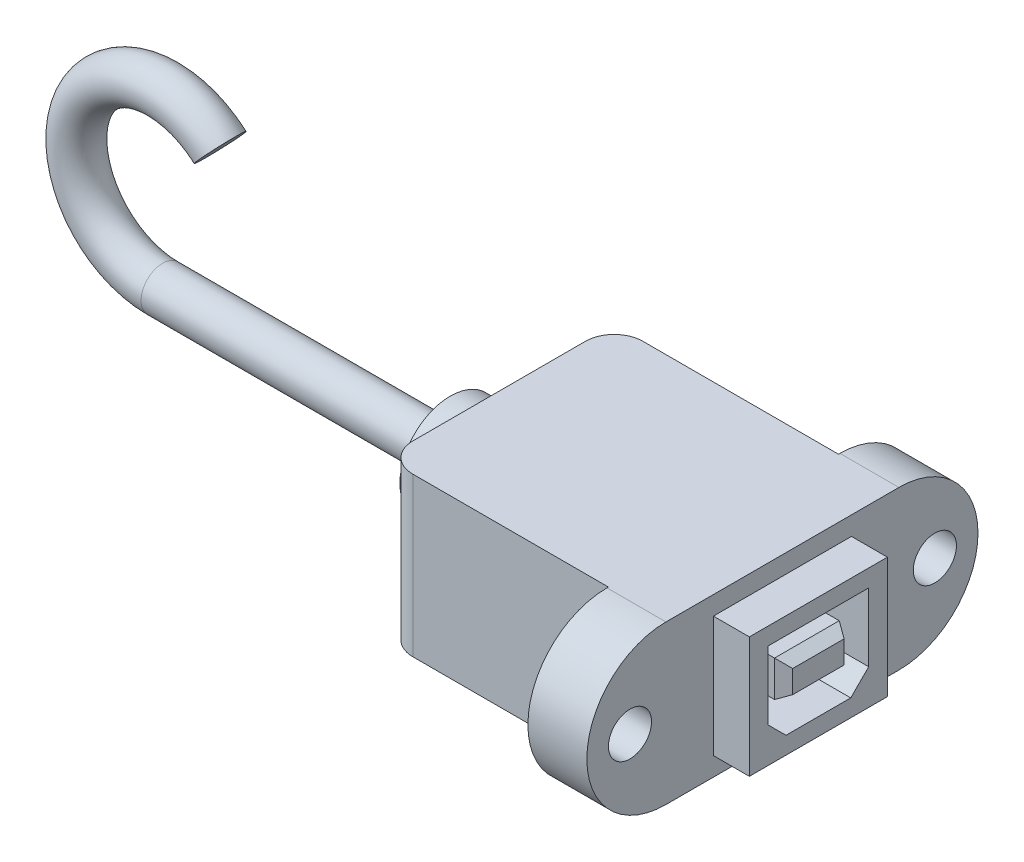
SolidWorks part; units mm, degrees
ref_plane "Front" through (0, 0, 0) normal (0, 0, 1) x (1, 0, 0)
ref_plane "Top" through (0, 0, 0) normal (0, 1, 0) x (1, 0, 0)
ref_plane "Right" through (0, 0, 0) normal (1, 0, 0) x (0, 0, -1)
sketch "Sketch1" plane through (0, 0, 0) normal (0, 1, 0) x (1, 0, 0)
  line L0 (0, 0) -> (0, 20.32)
  line L1 (0, 20.32) -> (19.812, 20.32)
  line L2 (19.812, 20.32) -> (19.812, 27.432)
  line L3 (19.812, 27.432) -> (25.019, 27.432)
  line L4 (25.019, 27.432) -> (25.019, -7.112)
  line L5 (25.019, -7.112) -> (19.812, -7.112)
  line L6 (19.812, -7.112) -> (19.812, 0)
  line L7 (19.812, 0) -> (0, 0)
  dimension "D1" = 34.544
  dimension "D2" = 5.207
  dimension "D3" = 20.32
  dimension "D4" = 19.812
extrude "Boss-Extrude1" add sketch "Sketch1" along normal blind 13.97
sketch "Sketch2" plane through (25.019, 0, 0) normal (1, 0, 0) x (0, 0, -1)
  line L0 (-7.112, 6.985) -> (4.064, 6.985) construction
  line L1 (4.064, 12.319) -> (16.256, 12.319)
  line L2 (4.064, 12.319) -> (4.064, 1.651)
  line L3 (4.064, 1.651) -> (16.256, 1.651)
  line L4 (16.256, 12.319) -> (16.256, 1.651)
  line L5 (-7.112, 13.97) -> (-7.112, 0) construction
  line L6 (4.064, 6.985) -> (10.16, 1.651) construction
  line L7 (10.16, 1.651) -> (10.16, 0) construction
  line L8 (-7.112, 0) -> (27.432, 0) construction
  dimension "D1" = 10.668
  dimension "D2" = 12.192
extrude "Boss-Extrude2" add sketch "Sketch2" along normal blind 3.175
sketch "Sketch3" plane through (28.194, 0, 0) normal (1, 0, 0) x (0, 0, -1)
  line L0 (5.715, 10.795) -> (14.605, 10.795)
  line L1 (14.605, 10.795) -> (14.605, 4.7625)
  line L2 (14.605, 4.7625) -> (13.0175, 3.175)
  line L3 (13.0175, 3.175) -> (7.3025, 3.175)
  line L4 (7.3025, 3.175) -> (5.715, 4.7625)
  line L5 (5.715, 4.7625) -> (5.715, 10.795)
  line L6 (10.16, 1.651) -> (10.16, 5.3975) construction
  line L7 (7.3025, 8.5725) -> (13.0175, 8.5725)
  line L8 (7.3025, 8.5725) -> (7.3025, 5.3975)
  line L9 (7.3025, 5.3975) -> (13.0175, 5.3975)
  line L10 (13.0175, 8.5725) -> (13.0175, 5.3975)
  line L11 (4.064, 1.651) -> (16.256, 1.651) construction
  line L12 (10.16, 5.3975) -> (7.3025, 6.985) construction
  line L13 (7.3025, 6.985) -> (4.064, 6.985) construction
  line L14 (4.064, 12.319) -> (4.064, 1.651) construction
  line L15 (13.0175, 3.175) -> (13.0175, 1.651) construction
  line L16 (4.064, 1.651) -> (16.256, 1.651) construction
  line L17 (10.16, 10.795) -> (10.16, 12.319) construction
  line L18 (16.256, 12.319) -> (4.064, 12.319) construction
  point P14 (10.16, 3.175)
  dimension "D1" = 5.715
  dimension "D2" = 3.175
  dimension "D3" = 7.62
  dimension "D4" = 8.89
  dimension "D5" = 135
  dimension "D6" = 1.5875
extrude "Cut-Extrude1" cut sketch "Sketch3" against normal blind 7.62
chamfer "Chamfer1" distance 1.016 angle 30 4 edges at (28.194, 6.985, -13.0175) (28.194, 5.3975, -10.16) (28.194, 6.985, -7.3025) (28.194, 8.5725, -10.16) first distance on face at (24.384, 6.985, -13.0175) first distance on face at (24.384, 5.3975, -10.16) first distance on face at (24.384, 6.985, -7.3025) first distance on face at (24.384, 8.5725, -10.16)
sketch "Sketch4" plane through (25.019, 0, 0) normal (1, 0, 0) x (0, 0, -1)
  line L0 (-7.112, 13.97) -> (27.432, 13.97) construction
  line L1 (-7.112, 0) -> (27.432, 0) construction
  line L2 (27.432, 13.97) -> (27.432, 0) construction
  line L3 (-7.112, 13.97) -> (-7.112, 0) construction
  line L4 (-0.127, 0) -> (-7.112, 0)
  line L5 (-7.112, 0) -> (-7.112, 13.97)
  line L6 (-7.112, 13.97) -> (-0.127, 13.97)
  line L7 (20.447, 13.97) -> (27.432, 13.97)
  line L8 (27.432, 13.97) -> (27.432, 0)
  line L9 (27.432, 0) -> (20.447, 0)
  line L10 (-3.302, 6.985) -> (10.16, 13.97) construction
  line L11 (10.16, 13.97) -> (23.622, 6.985) construction
  line L12 (25.527, 6.985) -> (27.432, 6.985) construction
  arc A0 (-0.127, 13.97) -> (-0.127, 0) centre (-0.127, 6.985) ccw
  arc A1 (20.447, 13.97) -> (20.447, 0) centre (20.447, 6.985) cw
  circle A4 centre (-3.302, 6.985) radius 1.905
  circle A5 centre (23.622, 6.985) radius 1.905
  line M3 (-7.112, 0) -> (27.432, 0)
  line M4 (27.432, 0) -> (27.432, 13.97)
  line M5 (27.432, 13.97) -> (-7.112, 13.97)
  line M6 (-7.112, 13.97) -> (-7.112, 0)
  dimension "D1" = 26.924
  dimension "D2" = 3.81
  dimension "D3" = 3.81
extrude "Cut-Extrude2" cut sketch "Sketch4" against normal through all contours A0 M5 M6 | A0 L5 M3 | A4 | A1 L8 M5 | A1 M4 M3 | A5 region at (25.019, 1.5602, 5.5518) region at (25.019, 12.4098, 5.5518) region at (25.019, 1.5602, -25.8718) region at (25.019, 12.4098, -25.8718) region at (25.019, 6.985, 3.302) region at (25.019, 6.985, -23.622)
fillet "Fillet1" radius 2.54 2 edges at (0, 6.985, 0) (0, 6.985, -20.32)
sketch "Sketch5" plane through (0, 0, 0) normal (-1, 0, 0) x (0, 0, 1)
  line L0 (-17.78, 6.985) -> (-10.16, 6.985) construction
  line L1 (-17.78, 13.97) -> (-17.78, 0) construction
  line L2 (-10.16, 6.985) -> (-10.16, 13.97) construction
  line L3 (-17.78, 13.97) -> (-2.54, 13.97) construction
  circle A0 centre (-10.16, 6.985) radius 4.445
  dimension "D1" = 8.89
extrude "Boss-Extrude3" add sketch "Sketch5" along normal blind 4.318
sketch "Sketch6" plane through (-4.318, 0, 0) normal (-1, 0, 0) x (0, 0, 1)
  circle A0 centre (-10.16, 6.985) radius 1.905
  circle A1 centre (-10.16, 6.985) radius 4.445 construction
  dimension "D1" = 3.81
ref_plane "Plane1" through (0, 0, -10.16) normal (0, 0, -1) x (-1, 0, 0)
sketch "Sketch7" plane through (0, 0, -10.16) normal (0, 0, -1) x (-1, 0, 0)
  line L0 (4.318, 6.985) -> (29.718, 6.985)
  line L1 (4.318, 5.08) -> (4.318, 8.89) construction
  arc A0 (29.718, 6.985) -> (24.638, 20.2846) centre (29.718, 14.605) ccw
  dimension "D1" = 7.62
  dimension "D2" = 5.08
  dimension "D3" = 25.4
sweep "Sweep1" add profiles "Sketch6" path "Sketch7"
